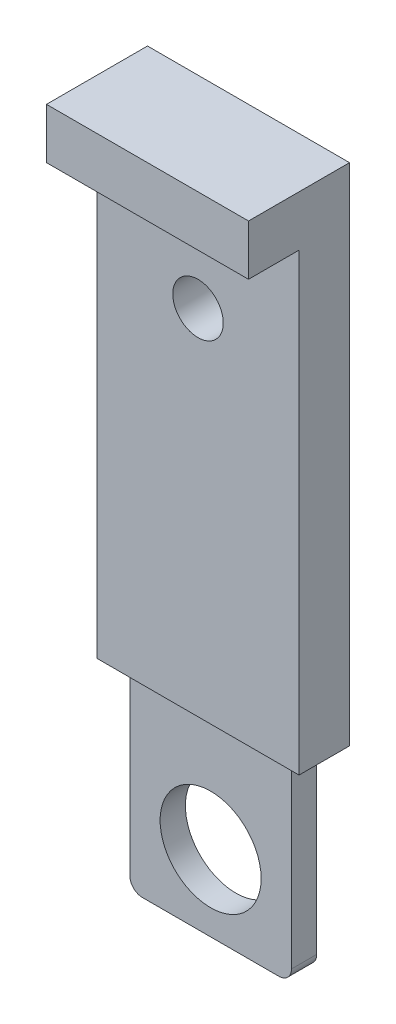
SolidWorks part; units mm, degrees
material "Czyste srebro"
ref_plane "Front Plane" through (0, 0, 0) normal (0, 0, 1) x (1, 0, 0)
ref_plane "Top Plane" through (0, 0, 0) normal (0, 1, 0) x (1, 0, 0)
ref_plane "Right Plane" through (0, 0, 0) normal (1, 0, 0) x (0, 0, -1)
sketch "Szkic1" plane through (0, 0, 0) normal (0, 1, 0) x (1, 0, 0)
  line L1 (-2, 0.5) -> (2, 0.5)
  line L2 (-2, 0.5) -> (-2, -0.5)
  line L3 (-2, -0.5) -> (2, -0.5)
  line L4 (2, 0.5) -> (2, -0.5)
  line L5 (-2, 0.5) -> (2, -0.5) construction
  line L6 (-2, -0.5) -> (2, 0.5) construction
  point P0 (0, 0)
extrude "Dodanie-wyciągnięcie1" add sketch "Szkic1" along normal blind 10 contours L3 L4 L1 L2
sketch "Szkic2" plane through (0, 0, -0.5) normal (0, 0, -1) x (-1, 0, 0)
  line L0 (0, 10) -> (0, 7) construction
  line L1 (2, 10) -> (-2, 10) construction
  circle A0 centre (0, 7) radius 0.5
extrude "Wytnij-wyciągnięcie1" cut sketch "Szkic2" against normal blind 10
sketch "Szkic3" plane through (0, 0, 0.5) normal (0, 0, 1) x (1, 0, 0)
  line L1 (2, 10) -> (-2, 10)
  line L2 (2, 10) -> (2, 9)
  line L3 (2, 9) -> (-2, 9)
  line L4 (-2, 10) -> (-2, 9)
extrude "Dodanie-wyciągnięcie2" add sketch "Szkic3" along normal blind 1
sketch "Szkic4" plane through (0, 0, 0) normal (0, -1, 0) x (-1, 0, 0)
  line L1 (-1.6, -0.25) -> (1.6, -0.25)
  line L2 (-1.6, -0.25) -> (-1.6, 0.25)
  line L3 (-1.6, 0.25) -> (1.6, 0.25)
  line L4 (1.6, -0.25) -> (1.6, 0.25)
  line L5 (-1.6, -0.25) -> (1.6, 0.25) construction
  line L6 (-1.6, 0.25) -> (1.6, -0.25) construction
  point P0 (0, 0)
extrude "Dodanie-wyciągnięcie3" add sketch "Szkic4" along normal blind 3.9
sketch "Szkic5" plane through (0, 0, 0.25) normal (0, 0, 1) x (1, 0, 0)
  line L0 (0, -3.9) -> (0, -2.4) construction
  line L1 (1.6, -3.9) -> (-1.6, -3.9) construction
  circle A0 centre (0, -2.4) radius 1
extrude "Wytnij-wyciągnięcie2" cut sketch "Szkic5" against normal blind 3.9
fillet "Zaokrąglenie1" radius 0.25 6 edges at (1.6, 0, 0) (0, 0, -0.25) (-1.6, 0, 0) (0, 0, 0.25) (-1.6, -3.9, 0) (1.6, -3.9, 0)
